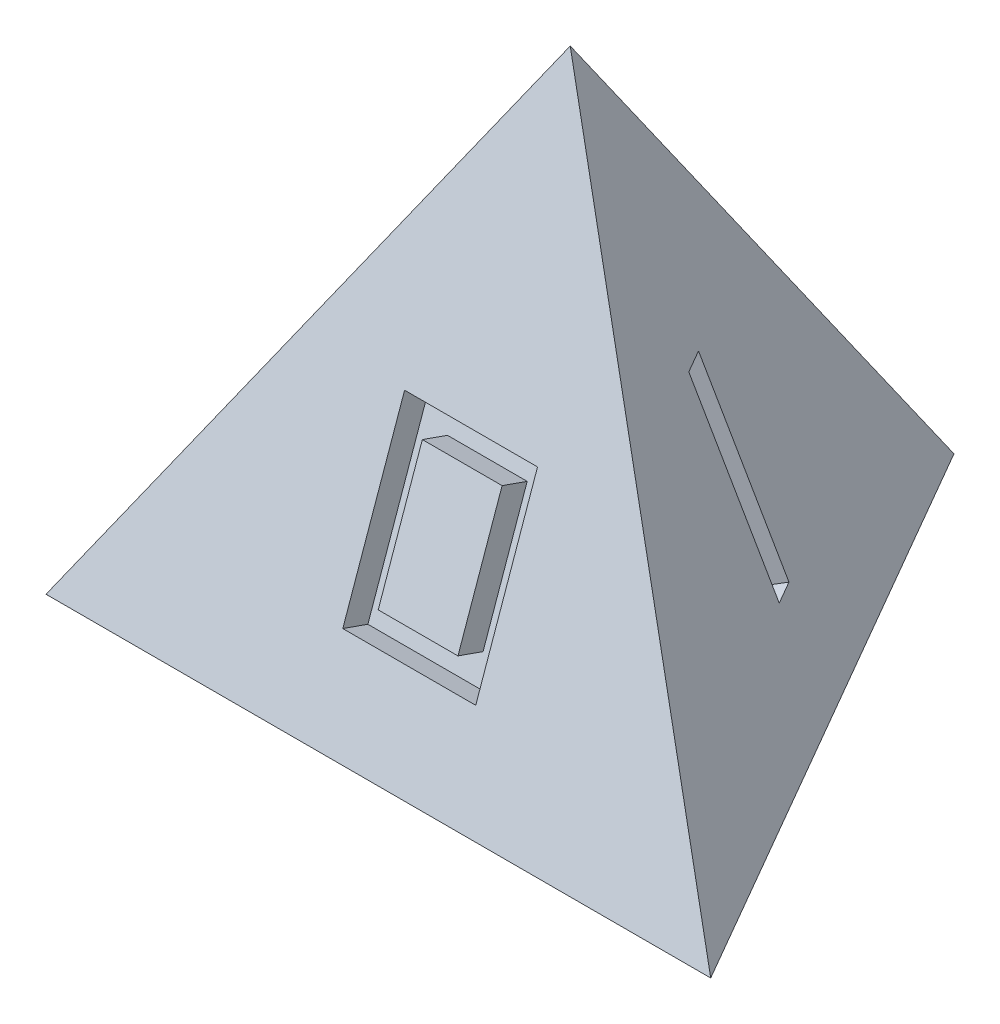
SolidWorks part; units mm, degrees
ref_plane "Front Plane" through (0, 0, 0) normal (0, 0, 1) x (1, 0, 0)
ref_plane "Top Plane" through (0, 0, 0) normal (0, 1, 0) x (1, 0, 0)
ref_plane "Right Plane" through (0, 0, 0) normal (1, 0, 0) x (0, 0, -1)
sketch "Sketch1" plane through (0, 0, 0) normal (0, 1, 0) x (1, 0, 0)
  line L1 (0, 7.3323) -> (-6.35, -3.6662)
  line L2 (-6.35, -3.6662) -> (6.35, -3.6662)
  line L3 (6.35, -3.6662) -> (0, 7.3323)
  circle A0 centre (0, 0) radius 3.6662 construction
  dimension "D1" = 12.7
ref_plane "Plane1" through (0, 10.414, 0) normal (0, 1, 0) x (1, 0, 0)
sketch "Sketch2" plane through (0, 10.414, 0) normal (0, 1, 0) x (1, 0, 0)
  point P0 (0, 0)
loft "Loft1" add profiles "Sketch2", "Sketch1"
ref_plane "Plane2" through (0, 5.334, 0) normal (0, 1, 0) x (1, 0, 0)
sketch "Sketch4" plane through (0, 1.1483, 3.2619) normal (0, 0.3321, 0.9433) x (1, 0, 0)
  line L0 (-1.016, 2.3386) -> (1.016, 2.3386)
  line L1 (1.016, 2.3386) -> (1.016, 3.8626)
  line L2 (1.016, 3.8626) -> (-1.016, 3.8626)
  line L3 (-1.016, 3.8626) -> (-1.016, 2.3386)
  line L4 (-1.016, 2.3386) -> (-1.016, 0.8146)
  line L5 (-6.35, -1.2174) -> (6.35, -1.2174) construction
  line L6 (-6.35, -1.2174) -> (6.35, -1.2174)
  line L7 (-1.016, 0.8146) -> (1.016, 0.8146)
  line L8 (1.016, 0.8146) -> (1.016, 2.3386)
  line L9 (1.27, 2.3386) -> (1.27, 4.1166)
  line L10 (1.27, 4.1166) -> (-1.27, 4.1166)
  line L11 (-1.27, 4.1166) -> (-1.27, 2.3386)
  line L12 (-1.016, 2.0846) -> (1.016, 2.0846)
  line L13 (-1.27, 2.3386) -> (-1.27, 0.5606)
  line L14 (-1.27, 0.5606) -> (1.27, 0.5606)
  line L15 (1.27, 0.5606) -> (1.27, 2.3386)
  line L16 (0.762, 2.3386) -> (0.762, 3.6086)
  line L17 (0.762, 3.6086) -> (-0.762, 3.6086)
  line L18 (-0.762, 3.6086) -> (-0.762, 2.3386)
  line L19 (-1.016, 2.5926) -> (1.016, 2.5926)
  line L20 (-0.762, 2.3386) -> (-0.762, 1.0686)
  line L21 (-0.762, 1.0686) -> (0.762, 1.0686)
  line L22 (0.762, 1.0686) -> (0.762, 2.3386)
  point P3 (0, 2.3386)
  point P11 (0, 0)
  dimension "D1" = 2.032
  dimension "D2" = 1.524
  dimension "D3" = 2.032
  dimension "D4" = 0.254
  dimension "D5" = 0.254
ref_axis "Axis1" through (0, 10.414, 0) along (0, 1, 0)
extrude "Cut-Extrude1" cut sketch "Sketch4" against normal blind 0.508 contours L14 L15 L9 L10 L11 L13 L8 L7 L4 L3 L2 L1 | L3 L19 L18 L17 L16 L1 L2 | L19 L3 L0 L18 | L20 L0 L4 L12 | L22 L21 L20 L12 L4 L7 L8 | L19 L16 L0 L1 | L22 L12 L8 L0 region at (-0.889, 3.474, 2.4432) region at (-0.889, 3.2344, 2.5275) region at (-0.992, 4.1928, 2.1901) region at (-0.889, 3.092, 2.5776) region at (0.889, 3.474, 2.4432) region at (0.889, 3.2344, 2.5275) region at (1.2263, 2.5157, 2.7806)
sketch "Sketch6" plane through (2.8249, 1.1483, -1.631) normal (0.8169, 0.3321, -0.4716) x (-0.4369, -0.1776, -0.8818)
  line L0 (-1.8496, 9.6474) -> (0.2292, -1.1956) construction
  line L1 (-0.8708, 4.5419) -> (-0.1534, 0.8)
  line L2 (-6.0072, -2.3913) -> (6.4656, 0) construction
  line L3 (-1.1202, 4.494) -> (-0.4028, 0.7522)
  line L4 (-0.6213, 4.5897) -> (0.0961, 0.8478)
  line L5 (-1.1202, 4.494) -> (-0.6213, 4.5897)
  line L6 (-0.4028, 0.7522) -> (0.0961, 0.8478)
  dimension "D1" = 3.81
  dimension "D2" = 2.032
  dimension "D3" = 0.254
  dimension "D4" = 0.254
extrude "Cut-Extrude2" cut sketch "Sketch6" against normal blind 0.508 contours L3 L6 L4 L5
sketch "Sketch7" plane through (-2.8249, 1.1483, -1.631) normal (-0.8169, 0.3321, -0.4716) x (-0.4369, 0.1776, 0.8818)
  line L0 (1.8496, 9.6474) -> (-0.2292, -1.1956) construction
  line L1 (-6.4656, 0) -> (6.0072, -2.3913) construction
  line L19 (1.2469, 1.1076) -> (1.1512, 0.6087)
  line L20 (-0.2705, 3.9848) -> (-0.3662, 3.4859)
  line L21 (1.9746, 3.5544) -> (-0.2705, 3.9848)
  line L22 (1.9746, 3.5544) -> (1.6398, 1.8082)
  line L23 (1.6398, 1.8082) -> (-0.3559, 2.1908)
  line L24 (-0.3559, 2.1908) -> (-0.4993, 1.4424)
  line L25 (1.2469, 1.1076) -> (-0.4993, 1.4424)
  line L26 (1.38, 3.1511) -> (-0.3662, 3.4859)
  line L27 (1.38, 3.1511) -> (1.2365, 2.4027)
  line L28 (1.2365, 2.4027) -> (-0.7591, 2.7853)
  line L29 (-0.7591, 2.7853) -> (-1.0939, 1.0391)
  line L30 (1.1512, 0.6087) -> (-1.0939, 1.0391)
  line L31 (-0.5575, 2.4881) -> (-0.7966, 1.2408)
  line L32 (1.6773, 3.3527) -> (1.4382, 2.1055)
  line L33 (1.199, 0.8582) -> (-0.7966, 1.2408)
  line L34 (1.4382, 2.1055) -> (-0.5575, 2.4881)
  line L35 (1.6773, 3.3527) -> (-0.3184, 3.7353)
  point P8 (0.6795, 3.544)
  point P11 (0.4403, 2.2968)
  point P14 (0.2012, 1.0495)
  dimension "D1" = 0.125
  dimension "D2" = 1.27
  dimension "D3" = 0.1723
  dimension "D4" = 0.2098
  dimension "D5" = 0.6027
extrude "Cut-Extrude3" cut sketch "Sketch7" against normal blind 0.508 contours L0 L21 L20 L35 | L0 L35 L20 L26 | L21 L0 L35 L32 L34 L23 L22 | L35 L0 L26 L27 L28 L34 L32 | L0 L28 L29 L30 L33 L31 L34 | L0 L34 L31 L33 L25 L24 L23 | L25 L0 L33 L19 | L33 L0 L30 L19 region at (-2.0389, 4.7678, -0.4439) region at (-1.4966, 4.6719, -1.4507) region at (-2.0466, 4.5343, -0.595) region at (-1.5697, 4.4324, -1.4928) region at (-2.1032, 3.474, -1.2436) region at (-2.0295, 3.1325, -1.6117) region at (-2.7351, 2.2761, -0.9925) region at (-2.8081, 2.0365, -1.0347)
sketch "Sketch8" plane through (0, 0, 0) normal (0, -1, 0) x (1, 0, 0)
  line L0 (-1.016, 1.1262) -> (1.016, 1.1262)
  line L1 (-6.35, 3.6662) -> (6.35, 3.6662) construction
  line L2 (-1.016, -0.1438) -> (1.016, -0.1438)
  line L7 (0, 3.6662) -> (0, -7.3323) construction
  line L8 (-1.016, -1.4138) -> (1.016, -1.4138)
  line L9 (-1.016, 1.1262) -> (-1.016, -1.4138)
  line L10 (-0.762, -1.1598) -> (1.016, -1.1598)
  line L11 (-0.762, 0.8722) -> (-0.762, -1.1598)
  line L12 (-0.762, 0.8722) -> (1.016, 0.8722)
  line L13 (-1.016, -0.3978) -> (1.016, -0.3978)
  line L14 (-1.27, -1.6678) -> (1.016, -1.6678)
  line L15 (-1.27, 1.3802) -> (-1.27, -1.6678)
  line L16 (-1.27, 1.3802) -> (1.016, 1.3802)
  line L17 (-1.016, 0.1102) -> (1.016, 0.1102)
  line L18 (1.016, -1.6678) -> (1.016, -1.1598)
  line L19 (1.016, -0.3978) -> (1.016, 0.1102)
  line L20 (1.016, 0.8722) -> (1.016, 1.3802)
  point P7 (0, 1.1262)
  point P10 (0, -0.1438)
  point P13 (0, -1.4138)
  dimension "D1" = 2.54
  dimension "D2" = 1.27
  dimension "D3" = 2.032
  dimension "D4" = 2.54
  dimension "D5" = 0.254
  dimension "D6" = 0.254
extrude "Cut-Extrude4" cut sketch "Sketch8" against normal blind 0.508 and the other way through all contours L7 L0 L9 L17 L11 L12 | L7 L16 L15 L14 L8 L9 L0 | L7 L17 L11 L2 | L7 L2 L11 L13 | L17 L7 L2 L19 | L2 L7 L13 L19 | L17 L9 L2 L11 | L9 L13 L11 L2 | L7 L10 L11 L13 L9 L8 | L10 L7 L8 L18 | L8 L7 L14 L18 | L0 L7 L12 L20 | L16 L7 L0 L20
